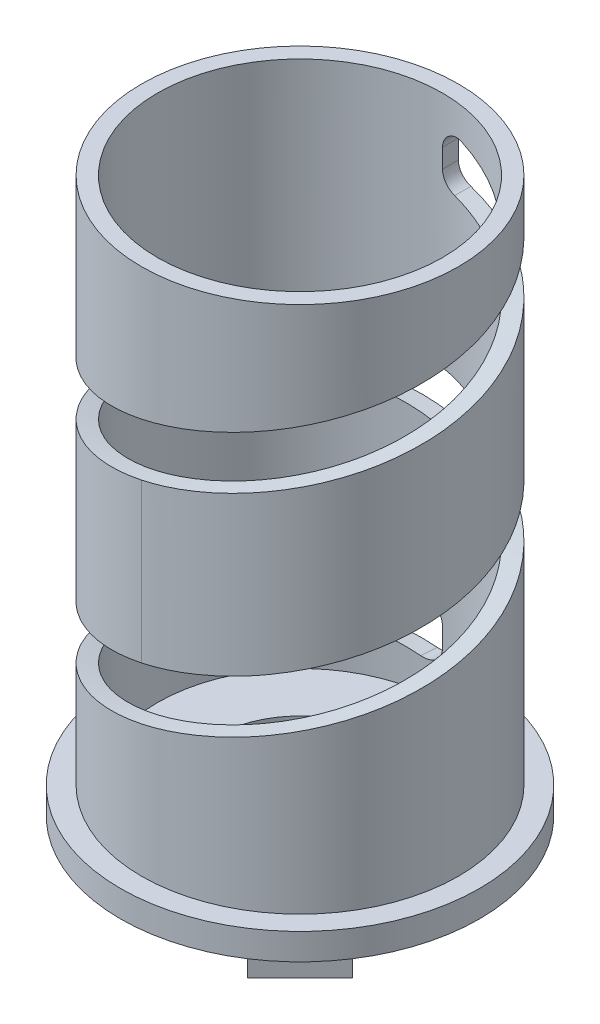
SolidWorks part; units mm, degrees
ref_plane "Front Plane" through (0, 0, 0) normal (0, 0, 1) x (1, 0, 0)
ref_plane "Top Plane" through (0, 0, 0) normal (0, 1, 0) x (1, 0, 0)
ref_plane "Right Plane" through (0, 0, 0) normal (1, 0, 0) x (0, 0, -1)
sketch "Sketch 1" plane through (0, 0, 0) normal (0, 1, 0) x (1, 0, 0)
  circle A0 centre (0, 0) radius 15
  dimension "D1" = 30
extrude "Boss-Extrude2" add sketch "Sketch 1" along normal blind 60
sketch "Sketch20" plane through (0, 60, 0) normal (0, 1, 0) x (1, 0, 0)
  circle A0 centre (0, 0) radius 13.5
  dimension "D1" = 27
extrude "Cut-Extrude1" cut sketch "Sketch20" against normal blind 60
ref_plane "Plane6" through (0, 55, 0) normal (0, 1, 0) x (1, 0, 0)
sketch "Sketch21" plane through (0, 55, 0) normal (0, 1, 0) x (1, 0, 0)
  circle A0 centre (0, 0) radius 15 construction
  circle A1 centre (0, 0) radius 15
curve "Helix/Spiral3" pitch 20 height 40 radius 15 centre (0, 55, 0) axis (0, -1, 0) start towards (0, 0, -1)
sketch "Sketch24" plane through (0, 0, 0) normal (1, 0, 0) x (0, 0, -1)
  line L1 (15, 57.5) -> (10, 57.5)
  line L2 (15, 57.5) -> (15, 52.5)
  line L3 (15, 52.5) -> (10, 52.5)
  line L4 (10, 57.5) -> (10, 52.5)
  point P4 (15, 55)
  dimension "D1" = 5
  dimension "D2" = 5
sweep "Cut-Sweep5" cut profiles "Sketch24" path "Helix/Spiral3" align with end faces yes
ref_plane "Plane2" through (0, 10, 0) normal (0, 1, 0) x (1, 0, 0)
sketch "Sketch26" plane through (0, 10, 0) normal (0, 1, 0) x (1, 0, 0)
  circle A0 centre (0, 0) radius 13.5 construction
  circle A1 centre (0, 0) radius 13.5
  circle A2 centre (0, 0) radius 15 construction
  circle A3 centre (0, 0) radius 15
extrude "Cut-Extrude2" cut sketch "Sketch26" against normal blind 10
ref_plane "Plane7" through (0, 0, -15) normal (0, 0, 1) x (1, 0, 0)
sketch "Sketch30" plane through (0, 10, 0) normal (0, -1, 0) x (1, 0, 0)
  circle A0 centre (0, 0) radius 17
  circle A1 centre (0, 0) radius 8
  dimension "D1" = 34
  dimension "D2" = 16
extrude "Boss-Extrude4" add sketch "Sketch30" along normal blind 2.5
sketch "Sketch31" plane through (0, 7.5, 0) normal (0, -1, 0) x (1, 0, 0)
  line L0 (-13.3157, 8.3659) -> (-9.7801, 4.8304)
  line L1 (-9.4045, 9.4045) -> (9.4045, 9.4045)
  line L2 (-9.4045, 9.4045) -> (-9.4045, -9.4045)
  line L3 (-9.4045, -9.4045) -> (9.4045, -9.4045)
  line L4 (9.4045, 9.4045) -> (9.4045, -9.4045)
  line L5 (-9.4045, 9.4045) -> (9.4045, -9.4045) construction
  line L6 (-9.4045, -9.4045) -> (9.4045, 9.4045) construction
  line L7 (-13.3157, 8.3659) -> (-8.3659, 13.3157)
  line L8 (-9.7801, 4.8304) -> (-4.8304, 9.7801)
  line L9 (-8.3659, 13.3157) -> (-4.8304, 9.7801)
  line L10 (4.8304, 9.7801) -> (8.3659, 13.3157)
  line L11 (4.8304, 9.7801) -> (9.7801, 4.8304)
  line L12 (8.3659, 13.3157) -> (13.3157, 8.3659)
  line L13 (9.7801, 4.8304) -> (13.3157, 8.3659)
  line L14 (-4.8304, -9.7801) -> (-8.3659, -13.3157)
  line L15 (-4.8304, -9.7801) -> (-9.7801, -4.8304)
  line L16 (-8.3659, -13.3157) -> (-13.3157, -8.3659)
  line L17 (-9.7801, -4.8304) -> (-13.3157, -8.3659)
  line L18 (4.8304, -9.7801) -> (8.3659, -13.3157)
  line L19 (4.8304, -9.7801) -> (9.7801, -4.8304)
  line L20 (8.3659, -13.3157) -> (13.3157, -8.3659)
  line L21 (9.7801, -4.8304) -> (13.3157, -8.3659)
  circle A0 centre (0, 0) radius 13.3
  point P7 (-11.5479, 6.5982)
  point P10 (-6.5982, 11.5479)
  point P13 (-7.3053, 7.3053)
  point P14 (11.5479, 6.5982)
  point P17 (6.5982, 11.5479)
  point P20 (7.3053, 7.3053)
  point P21 (-11.5479, -6.5982)
  point P24 (-6.5982, -11.5479)
  point P27 (-7.3053, -7.3053)
  point P28 (6.5982, -11.5479)
  point P31 (11.5479, -6.5982)
  dimension "D1" = 26.6
  dimension "D2" = 7
  dimension "D3" = 5
  dimension "D4" = 7
  dimension "D5" = 5
  dimension "D6" = 7
  dimension "D7" = 5
  dimension "D8" = 7
  dimension "D9" = 5
extrude "Boss-Extrude5" add sketch "Sketch31" along normal blind 2.5 contours L4 A0 L21 L19 | L19 L3 L4 | L18 A0 L3 L19 | A0 L18 L20 L21 | A0 L17 L16 L14 | L17 A0 L2 L15 | L3 L15 L2 | L3 A0 L14 L15 | L2 A0 L0 L8 | L2 L8 L1 | L9 A0 L1 L8 | A0 L9 L7 L0 | L1 L11 L4 | L13 A0 L4 L11 | L1 A0 L10 L11 | A0 L13 L12 L10 region at (-10.0647, 7.5, 10.0647) region at (-10.1544, 7.5, 6.9324) region at (-6.9324, 7.5, 10.1544) region at (-8.005, 7.5, 8.005) region at (-10.0647, 7.5, -10.0647) region at (-10.1544, 7.5, -6.9324) region at (-8.005, 7.5, -8.005) region at (-6.9324, 7.5, -10.1544) region at (6.9324, 7.5, 10.1544) region at (10.0647, 7.5, 10.0647) region at (8.005, 7.5, 8.005) region at (10.1544, 7.5, 6.9324) region at (8.005, 7.5, -8.005) region at (6.9324, 7.5, -10.1544) region at (10.0647, 7.5, -10.0647) region at (10.1544, 7.5, -6.9324)
scale "Scale1" scale about centroid uniform scaling yes scale factor 0.8
fillet "Fillet1" radius 1.25 4 edges at (0, 19.4925, -11.4) (0, 15.4925, -11.4) (0, 51.4925, -11.4) (0, 47.4925, -11.4)
